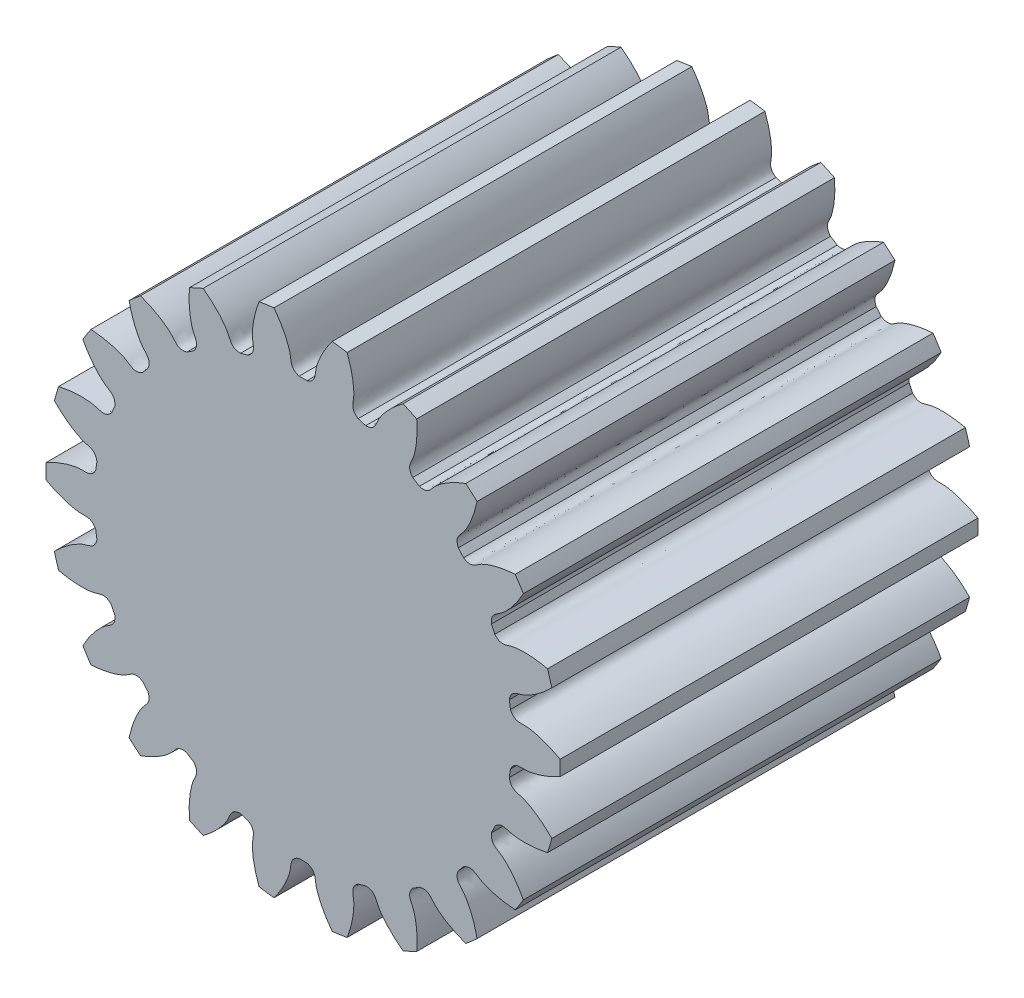
SolidWorks part; units mm, degrees
ref_plane "前视基准面" through (0, 0, 0) normal (0, 0, 1) x (1, 0, 0)
ref_plane "上视基准面" through (0, 0, 0) normal (0, 1, 0) x (1, 0, 0)
ref_plane "右视基准面" through (0, 0, 0) normal (1, 0, 0) x (0, 0, -1)
sketch "草图1" plane through (0, 0, 0) normal (0, 0, 1) x (1, 0, 0)
  circle A0 centre (0, 0) radius 12
extrude "凸台-拉伸1" add sketch "草图1" along normal blind 30
ref_axis "基准轴1" through (0, 0, -1.5) along (0, 0, 1)
sketch "草图2" plane through (0, 0, 0) normal (0, 0, 1) x (1, 0, 0)
  line L0 (0, 0) -> (0, 12) construction
  circle A0 centre (0, 0) radius 12 construction
  arc A1 (0.1857, 9.7482) -> (-0.1857, 9.7482) centre (0, 0) ccw
  arc A2 (3.0856, 13.5599) -> (-3.0856, 13.5599) centre (0, 0) ccw
  spline S0 degree 3 poles (0.1857, 9.7482) (0.5882, 9.8762) (0.5483, 10.1518) (0.5996, 10.4216) (0.606, 10.4519) (0.6139, 10.4862) (0.6235, 10.5243) (0.6349, 10.5661) (0.6484, 10.6117) (0.664, 10.661) (0.6819, 10.7139) (0.7023, 10.7703) (0.7253, 10.8301) (0.7511, 10.8933) (0.7797, 10.9597) (0.8114, 11.0293) (0.8462, 11.1021) (0.8843, 11.1778) (0.9259, 11.2563) (0.9711, 11.3377) (1.0199, 11.4217) (1.0726, 11.5082) (1.1292, 11.5972) (1.1899, 11.6884) (1.2547, 11.7818) (1.3238, 11.8773) (1.3973, 11.9746) (1.4753, 12.0737) (1.5579, 12.1744) (1.6452, 12.2766) (1.7372, 12.3802) (1.8341, 12.4849) (1.9359, 12.5906) (2.0428, 12.6972) (2.1547, 12.8044) (2.2718, 12.9123) (2.3942, 13.0205) (2.5218, 13.1289) (2.6548, 13.2373) (2.8415, 13.3834) (2.9864, 13.49) (3.0856, 13.5599) knots 0 0 0 0 0.157021 0.162531 0.168888 0.176093 0.184146 0.193046 0.202794 0.213389 0.224833 0.237123 0.250262 0.264248 0.279082 0.294763 0.311292 0.328669 0.346893 0.365965 0.385884 0.406652 0.428266 0.450729 0.474039 0.498197 0.523202 0.549055 0.575756 0.603304 0.6317 0.660944 0.691035 0.721974 0.75376 0.786395 0.819876 0.854206 0.889383 0.925408 1 1 1 1
  spline S1 degree 3 poles (-0.1857, 9.7482) (-0.5882, 9.8762) (-0.5483, 10.1518) (-0.5996, 10.4216) (-0.606, 10.4519) (-0.6139, 10.4862) (-0.6235, 10.5243) (-0.6349, 10.5661) (-0.6484, 10.6117) (-0.664, 10.661) (-0.6819, 10.7139) (-0.7023, 10.7703) (-0.7253, 10.8301) (-0.7511, 10.8933) (-0.7797, 10.9597) (-0.8114, 11.0293) (-0.8462, 11.1021) (-0.8843, 11.1778) (-0.9259, 11.2563) (-0.9711, 11.3377) (-1.0199, 11.4217) (-1.0726, 11.5082) (-1.1292, 11.5972) (-1.1899, 11.6884) (-1.2547, 11.7818) (-1.3238, 11.8773) (-1.3973, 11.9746) (-1.4753, 12.0737) (-1.5579, 12.1744) (-1.6452, 12.2766) (-1.7372, 12.3802) (-1.8341, 12.4849) (-1.9359, 12.5906) (-2.0428, 12.6972) (-2.1547, 12.8044) (-2.2718, 12.9123) (-2.3942, 13.0205) (-2.5218, 13.1289) (-2.6548, 13.2373) (-2.8415, 13.3834) (-2.9864, 13.49) (-3.0856, 13.5599) knots 0 0 0 0 0.157021 0.162531 0.168888 0.176093 0.184146 0.193046 0.202794 0.213389 0.224833 0.237123 0.250262 0.264248 0.279082 0.294763 0.311292 0.328669 0.346893 0.365965 0.385884 0.406652 0.428266 0.450729 0.474039 0.498197 0.523202 0.549055 0.575756 0.603304 0.6317 0.660944 0.691035 0.721974 0.75376 0.786395 0.819876 0.854206 0.889383 0.925408 1 1 1 1
extrude "切除-拉伸1" cut sketch "草图2" along normal through all
pattern_circular "阵列(圆周)1" count 22 every 16.364 about axis through (0, 0, -1.5) along (0, 0, 1) of "切除-拉伸1"
sketch "草图3" plane through (0, 0, 0) normal (0, 0, 1) x (1, 0, 0)
  circle A0 centre (0, 0) radius 11 construction
  dimension "Dn" = 22
sketch "草图4" plane through (0, 0, 30) normal (0, 0, 1) x (1, 0, 0)
  circle A0 centre (0, 0) radius 17.7866
extrude "切除-拉伸2" cut sketch "草图4" against normal offset from surface (10.5 mm away) 19.5 up to face at (0, 0, 0)
